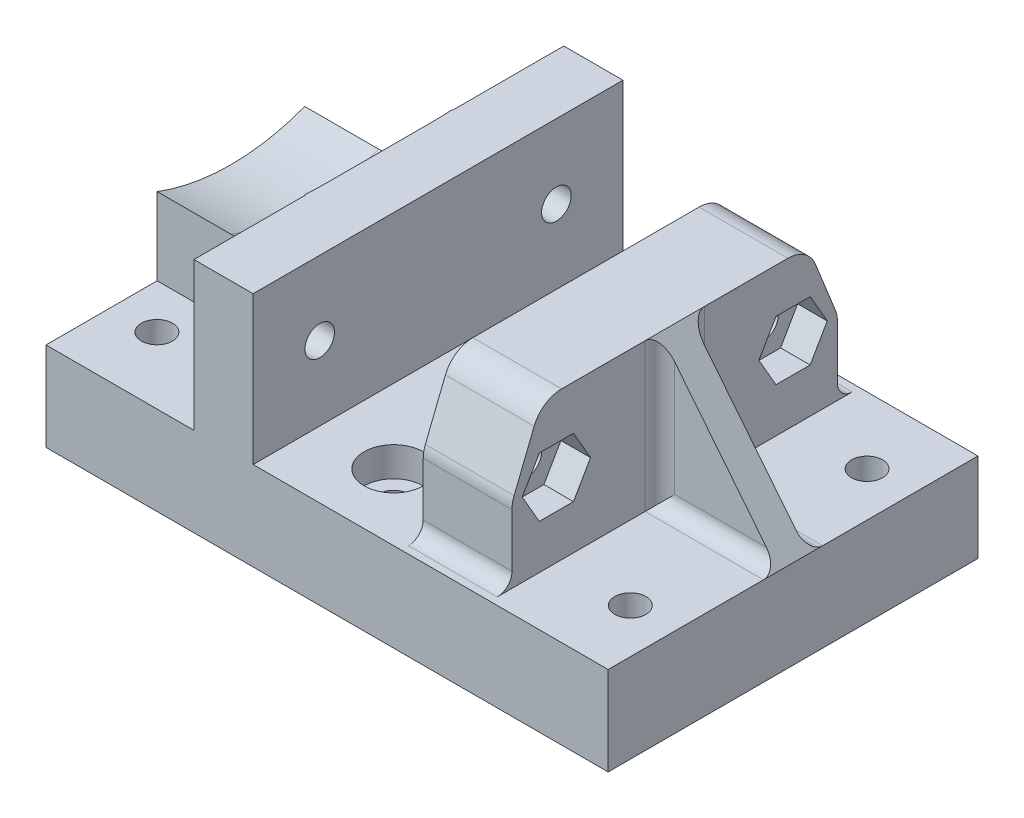
SolidWorks part; units mm, degrees
material "ABS PC"
ref_plane "Front Plane" through (0, 0, 0) normal (0, 0, 1) x (1, 0, 0)
ref_plane "Top Plane" through (0, 0, 0) normal (0, 1, 0) x (1, 0, 0)
ref_plane "Right Plane" through (0, 0, 0) normal (1, 0, 0) x (0, 0, -1)
sketch "Sketch1" plane through (0, 0, 0) normal (0, 1, 0) x (1, 0, 0)
  line L44 (17.7, -2.1) -> (18, -2.1) construction
  line L45 (19, -4.5) -> (19, 5)
  line L46 (19, 5) -> (19, 12.5)
  line L47 (19, 12.5) -> (-19, 12.5)
  line L48 (-19, 12.5) -> (-19, 5)
  line L49 (-19, 5) -> (-19, -4.5)
  line L50 (-18, -2.1) -> (-17.7, -2.1) construction
  line L51 (-17.7, -0.9) -> (-17.8, -0.9) construction
  line L52 (-17.8, -0.9) -> (-17.8, 3) construction
  line L53 (-17.3, 3.5) -> (-15.3, 3.5) construction
  line L54 (-14.8, 3) -> (-14.8, -1.5) construction
  line L55 (-16.8, -3.5) -> (-18, -3.5) construction
  line L56 (-19, -4.5) -> (-19, -5)
  line L57 (-19, -5) -> (-19, -12.5)
  line L58 (-19, -12.5) -> (19, -12.5)
  line L59 (19, -12.5) -> (19, -5)
  line L60 (19, -5) -> (19, -4.5)
  line L61 (18, -3.5) -> (16.8, -3.5) construction
  line L62 (14.8, -1.5) -> (14.8, 3) construction
  line L63 (15.3, 3.5) -> (17.3, 3.5) construction
  line L64 (17.8, 3) -> (17.8, -0.9) construction
  line L65 (17.8, -0.9) -> (17.7, -0.9) construction
  circle A2 centre (8, -8) radius 1.05 construction
  circle A4 centre (16, -8) radius 1.05
  circle A6 centre (0, -8) radius 1.05
  circle A8 centre (8, 0) radius 1.05 construction
  circle A10 centre (8, 8) radius 1.05 construction
  arc A24 (18, -2.1) -> (19, -1.1) centre (18, -1.1) ccw construction
  arc A25 (-19, -1.1) -> (-18, -2.1) centre (-18, -1.1) ccw construction
  arc A26 (-17.7, -2.1) -> (-17.7, -0.9) centre (-17.7, -1.5) ccw construction
  arc A27 (-17.3, 3.5) -> (-17.8, 3) centre (-17.3, 3) ccw construction
  arc A28 (-14.8, 3) -> (-15.3, 3.5) centre (-15.3, 3) ccw construction
  arc A29 (-16.8, -3.5) -> (-14.8, -1.5) centre (-16.8, -1.5) ccw construction
  arc A30 (-18, -3.5) -> (-19, -4.5) centre (-18, -4.5) ccw construction
  arc A31 (19, -4.5) -> (18, -3.5) centre (18, -4.5) ccw construction
  arc A32 (14.8, -1.5) -> (16.8, -3.5) centre (16.8, -1.5) ccw construction
  arc A33 (15.3, 3.5) -> (14.8, 3) centre (15.3, 3) ccw construction
  arc A34 (17.8, 3) -> (17.3, 3.5) centre (17.3, 3) ccw construction
  arc A35 (17.7, -0.9) -> (17.7, -2.1) centre (17.7, -1.5) ccw construction
  circle A36 centre (16, 8) radius 1.05
  circle A38 centre (0, 8) radius 1.05
  circle A40 centre (-8, 0) radius 1.05 construction
  circle A42 centre (-8, -8) radius 1.05 construction
  circle A44 centre (-16, -8) radius 1.05
  circle A46 centre (-16, 8) radius 1.05
  circle A48 centre (-8, 8) radius 1.05 construction
extrude "Boss-Extrude1" add sketch "Sketch1" along normal blind 6
sketch "Sketch2" plane through (0, 6, 0) normal (0, 1, 0) x (1, 0, 0)
  line L0 (19, 12.5) -> (-19, 12.5) construction
  line L1 (-19, -12.5) -> (-5, -12.5)
  line L2 (-19, -12.5) -> (-19, 12.5)
  line L3 (-19, 12.5) -> (-5, 12.5)
  line L4 (-5, -12.5) -> (-5, 12.5)
  line L5 (19, 0) -> (-19, 0) construction
  line L6 (11, -11) -> (5, -11)
  line L7 (11, -11) -> (11, 11)
  line L8 (11, 11) -> (5, 11)
  line L9 (5, -11) -> (5, 11)
  line L10 (19, -12.5) -> (19, 12.5) construction
  point P17 (5, 0)
  point P18 (11, 0)
  dimension "D1" = 8
  dimension "D2" = 14
  dimension "D3" = 6
  dimension "D4" = 11
extrude "Boss-Extrude2" add sketch "Sketch2" along normal blind 10
fillet "Fillet1" radius 1 2 edges at (8, 6, 11) (8, 6, -11)
sketch "Sketch7" plane through (11, 0, 0) normal (1, 0, 0) x (0, 0, -1)
  line L0 (-11, 11) -> (-9, 16)
  line L1 (-9, 16) -> (9, 16)
  line L2 (11, 11) -> (9, 16)
  line L4 (-12, 6) -> (12, 6)
  line L5 (11, 7) -> (11, 16)
  line L6 (11, 16) -> (-11, 16)
  line L7 (-11, 16) -> (-11, 7)
  line L8 (-12, 6) -> (12, 6) construction
  line L9 (11, 7) -> (11, 16) construction
  line L10 (11, 16) -> (-11, 16) construction
  line L11 (-11, 16) -> (-11, 7) construction
  line L12 (0, 6) -> (0, 16) construction
  line L13 (-11, 11) -> (-12.2224, 11)
  line L14 (-12.2224, 11) -> (-12.2224, 19.9984)
  line L15 (-12.2224, 19.9984) -> (15.4874, 19.9984)
  line L16 (15.4874, 19.9984) -> (15.4874, 11)
  line L17 (15.4874, 11) -> (11, 11)
  arc A2 (11, 7) -> (12, 6) centre (12, 7) ccw
  arc A3 (-12, 6) -> (-11, 7) centre (-12, 7) ccw
  arc A4 (11, 7) -> (12, 6) centre (12, 7) ccw construction
  arc A5 (-12, 6) -> (-11, 7) centre (-12, 7) ccw construction
  point P15 (0, 11)
  dimension "D2" = 5
  dimension "D3" = 18
  dimension "D1" = 0
extrude "Cut-Extrude2" cut sketch "Sketch7" against normal up to next contours L14 L15 L16 L17 L2 L1 L0 L13
fillet "Fillet2" radius 2 4 edges at (8, 11, 11) (8, 16, 9) (8, 16, -9) (8, 11, -11)
sketch "Sketch8" plane through (11, 0, 0) normal (1, 0, 0) x (0, 0, -1)
  line L0 (0, 6) -> (0, 16) construction
  line L1 (-12, 6) -> (12, 6) construction
  line L2 (-7.6459, 16) -> (7.6459, 16) construction
  line L3 (-8, 11) -> (0, 11) construction
  line L4 (-5.6906, 11) -> (-6.8453, 13)
  line L5 (-6.8453, 13) -> (-9.1547, 13)
  line L6 (-9.1547, 13) -> (-10.3094, 11)
  line L7 (-10.3094, 11) -> (-9.1547, 9)
  line L8 (-9.1547, 9) -> (-6.8453, 9)
  line L9 (-6.8453, 9) -> (-5.6906, 11)
  circle A0 centre (-8, 11) radius 2 construction
  dimension "D1" = 4
  dimension "D2" = 5
  dimension "D3" = 8
extrude "Cut-Extrude3" cut sketch "Sketch8" against normal blind 2
sketch "Sketch9" plane through (9, 0, 0) normal (1, 0, 0) x (0, 0, -1)
  line L6 (-6.8453, 9) -> (-5.6906, 11)
  line L7 (-5.6906, 11) -> (-6.8453, 13)
  line L8 (-6.8453, 13) -> (-9.1547, 13)
  line L9 (-9.1547, 13) -> (-10.3094, 11)
  line L10 (-10.3094, 11) -> (-9.1547, 9)
  line L11 (-9.1547, 9) -> (-6.8453, 9)
  line L12 (-6.8453, 9) -> (-5.6906, 11)
  line L13 (-5.6906, 11) -> (-6.8453, 13)
  line L14 (-6.8453, 13) -> (-9.1547, 13)
  line L15 (-9.1547, 13) -> (-10.3094, 11)
  line L16 (-10.3094, 11) -> (-9.1547, 9)
  line L17 (-9.1547, 9) -> (-6.8453, 9)
  circle A0 centre (-8, 11) radius 1
  dimension "D2" = 2
  dimension "D1" = 0
extrude "Cut-Extrude4" cut sketch "Sketch9" against normal up to next contours A0
ref_plane "Plane1" through (0, 0, 0) normal (0, 0, 1) x (1, 0, 0)
mirror "Mirror1" about plane through (0, 0, 0) normal (0, 0, 1) of "Cut-Extrude4", "Cut-Extrude3"
sketch "Sketch11" plane through (0, 0, 0) normal (0, 0, 1) x (1, 0, 0)
  line L0 (19, 6) -> (11, 16)
  line L1 (19, 6) -> (11, 6)
  line L2 (11, 6) -> (11, 16)
extrude "Boss-Extrude3" add sketch "Sketch11" along normal mid plane 2 contours L0 L2 L1
fillet "Fillet3" radius 1 4 edges at (11, 11, 1) (15, 6, 1) (11, 11, -1) (15, 6, -1)
sketch "Sketch13" plane through (0, 6, 0) normal (0, 1, 0) x (1, 0, 0)
  circle A0 centre (0, -8) radius 2
  circle A1 centre (0, 8) radius 2
  dimension "D1" = 4
  dimension "D2" = 4
extrude "Cut-Extrude5" cut sketch "Sketch13" against normal blind 2
sketch "Sketch14" plane through (-19, 0, 0) normal (-1, 0, 0) x (0, 0, 1)
  line L0 (-4.9878, 11.2186) -> (-4.9878, 6)
  line L1 (0, 0) -> (0, 27.6554) construction
  line L3 (-4.9878, 6) -> (-16.5281, 6)
  line L4 (-16.5281, 6) -> (-16.5281, 44.0405)
  line L5 (-16.5281, 44.0405) -> (16.5281, 44.0405)
  line L6 (0, -201000) -> (0, 249000) construction
  line L8 (16.5281, 6) -> (16.5281, 44.0405)
  line L9 (4.9878, 6) -> (16.5281, 6)
  line L10 (4.9878, 11.2186) -> (4.9878, 6)
  line L12 (12.5, 6) -> (2, 6) construction
  line L13 (12.5, 6) -> (2, 6) construction
  arc A0 (-4.9878, 11.2186) -> (4.9878, 11.2186) centre (0, 24.3) ccw
  point P14 (0, 44.0405)
  dimension "D1" = 14
extrude "Cut-Extrude6" cut sketch "Sketch14" against normal blind 10
sketch "Sketch15" plane through (-5, 0, 0) normal (1, 0, 0) x (0, 0, -1)
  circle A0 centre (-8, 11) radius 1 construction
  circle A1 centre (8, 11) radius 1 construction
  circle A2 centre (-8, 11) radius 1
  circle A3 centre (8, 11) radius 1
extrude "Cut-Extrude7" cut sketch "Sketch15" against normal through all
fillet "Fillet4" radius 5 1 edges at (-9, 10.3, 0)
